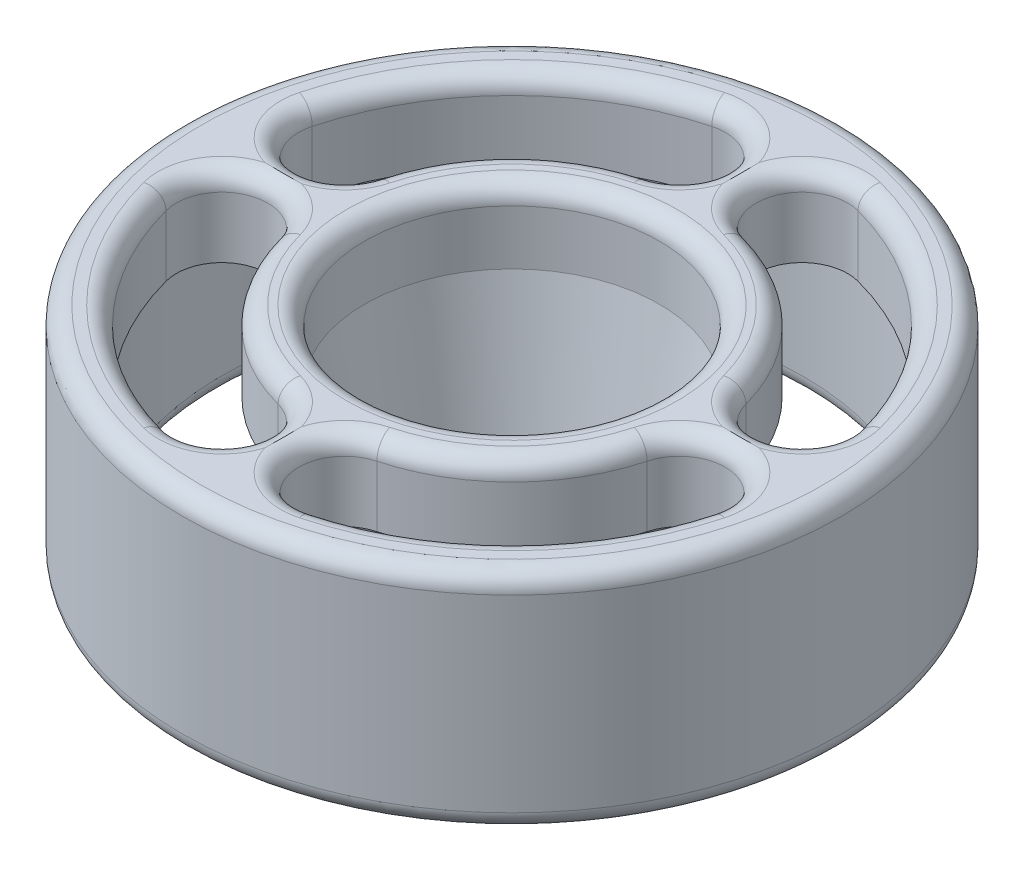
SolidWorks part; units mm, degrees
ref_plane "Front" through (0, 0, 0) normal (0, 0, 1) x (1, 0, 0)
ref_plane "Top" through (0, 0, 0) normal (0, 1, 0) x (1, 0, 0)
ref_plane "Right" through (0, 0, 0) normal (1, 0, 0) x (0, 0, -1)
sketch "Croquis1" plane through (0, 0, 0) normal (1, 0, 0) x (0, 0, -1)
  line L0 (-319.2356, 0) -> (15642.5458, 0) construction
  line L1 (0, -319.2356) -> (0, 15642.5458) construction
  line L3 (-6.6806, 2) -> (-8.0912, 10)
  line L4 (-8.0912, 10) -> (-8.0912, 14)
  line L5 (-8.0912, 14) -> (-18.0912, 14)
  line L6 (-18.0912, 14) -> (-18.0912, -2.75)
  line L7 (-319.2356, 2) -> (15642.5458, 2) construction
  line L8 (-6.6806, 2) -> (0, 2)
  line L9 (0, 2) -> (0, 0)
  line L10 (0, 0) -> (-3.25, 0)
  line L11 (-3.25, 0) -> (-3.25, -2.75)
  line L12 (-3.25, -2.75) -> (-18.0912, -2.75)
  dimension "D1" = 2
  dimension "D2" = 3.25
  dimension "D3" = 4
  dimension "D4" = 100
  dimension "D5" = 10
  dimension "D6" = 8
  dimension "D7" = 2.75
revolve "Revolución1" add sketch "Croquis1" angle 360 about L9
sketch "Croquis2" plane through (0, 2, 0) normal (0, 1, 0) x (1, 0, 0)
  circle A0 centre (0, 0) radius 1.125
  dimension "D1" = 2.25
extrude "Cortar-Extruir1" cut sketch "Croquis2" against normal through all
sketch "Croquis3" plane through (0, 0, 0) normal (1, 0, 0) x (0, 0, -1)
  line L0 (-1005.9461, -4.3493) -> (48994.0539, -4.3493) construction
  line L2 (-15.9567, -4.3493) -> (-15.9567, 9.6507)
  line L3 (-15.9567, 9.6507) -> (-9.9567, 9.6507)
  line L4 (-9.9567, 9.6507) -> (-7.9567, -4.3493)
  line L5 (0, -1000) -> (0, 49000) construction
  line L7 (-15.9567, -4.3493) -> (-7.9567, -4.3493)
  dimension "D1" = 14
  dimension "D2" = 8
  dimension "D3" = 6
revolve "Cortar-Revolución1" cut sketch "Croquis3" angle 360 about L5
sketch "Croquis5" plane through (0, 14, 0) normal (0, 1, 0) x (1, 0, 0)
  line L0 (-1000, 0) -> (49000, 0) construction
  line L1 (0, -1000) -> (0, 49000) construction
  line L2 (-707.1068, -707.1068) -> (34648.2323, 34648.2323) construction
  line L3 (-707.1068, 707.1068) -> (34648.2323, -34648.2323) construction
  line L4 (-702.5106, -711.703) -> (34652.8285, 34643.6361) construction
  line L5 (-711.703, -702.5106) -> (34643.6361, 34652.8285) construction
  circle A0 centre (0, 0) radius 13 construction
  circle A1 centre (0, 0) radius 15.5 construction
  circle A2 centre (0, 0) radius 10.5 construction
  arc A3 (3.3646, 12.557) -> (12.557, 3.3646) centre (0, 0) cw construction
  arc A4 (14.9835, 4.0148) -> (4.0148, 14.9835) centre (0, 0) ccw
  arc A5 (10.1306, 2.7145) -> (2.7145, 10.1306) centre (0, 0) ccw
  arc A6 (10.1306, 2.7145) -> (14.9835, 4.0148) centre (12.557, 3.3646) ccw
  arc A7 (4.0148, 14.9835) -> (2.7145, 10.1306) centre (3.3646, 12.557) ccw
  arc A8 (12.557, -3.3646) -> (3.3646, -12.557) centre (0, 0) cw construction
  arc A9 (4.0148, -14.9835) -> (14.9835, -4.0148) centre (0, 0) ccw
  arc A10 (2.7145, -10.1306) -> (10.1306, -2.7145) centre (0, 0) ccw
  arc A11 (2.7145, -10.1306) -> (4.0148, -14.9835) centre (3.3646, -12.557) ccw
  arc A12 (14.9835, -4.0148) -> (10.1306, -2.7145) centre (12.557, -3.3646) ccw
  arc A13 (-3.3646, -12.557) -> (-12.557, -3.3646) centre (0, 0) cw construction
  arc A14 (-14.9835, -4.0148) -> (-4.0148, -14.9835) centre (0, 0) ccw
  arc A15 (-10.1306, -2.7145) -> (-2.7145, -10.1306) centre (0, 0) ccw
  arc A16 (-10.1306, -2.7145) -> (-14.9835, -4.0148) centre (-12.557, -3.3646) ccw
  arc A17 (-4.0148, -14.9835) -> (-2.7145, -10.1306) centre (-3.3646, -12.557) ccw
  arc A18 (-12.557, 3.3646) -> (-3.3646, 12.557) centre (0, 0) cw construction
  arc A19 (-4.0148, 14.9835) -> (-14.9835, 4.0148) centre (0, 0) ccw
  arc A20 (-2.7145, 10.1306) -> (-10.1306, 2.7145) centre (0, 0) ccw
  arc A21 (-2.7145, 10.1306) -> (-4.0148, 14.9835) centre (-3.3646, 12.557) ccw
  arc A22 (-14.9835, 4.0148) -> (-10.1306, 2.7145) centre (-12.557, 3.3646) ccw
  point P22 (9.1924, 9.1924)
  point P32 (9.1924, -9.1924)
  point P39 (-9.1924, -9.1924)
  point P46 (-9.1924, 9.1924)
  point P51 (0, 0)
  dimension "D1" = 26
  dimension "D2" = 2.5
  dimension "D3" = 2.5
  dimension "D4" = 6.5
  dimension "D5" = 6.5
  dimension "D6" = 4
extrude "Cortar-Extruir3" cut sketch "Croquis5" against normal blind 12
fillet "Redondeo1" radius 1 20 edges at (0, 14, 8.0912) (-0.9382, 14, -13.2072) (-13.2072, 14, -0.9382) (-7.4161, 14, -7.4161) (-10.9687, 14, -10.9687) (0, 14, 18.0912) (0.9382, 14, -13.2072) (10.9687, 14, -10.9687) (7.4161, 14, -7.4161) (13.2072, 14, -0.9382) (13.2072, 14, 0.9382) (7.4161, 14, 7.4161) (10.9687, 14, 10.9687) (0.9382, 14, 13.2072) (-0.9382, 14, 13.2072) (-10.9687, 14, 10.9687) (-13.2072, 14, 0.9382) (-7.4161, 14, 7.4161) (0, -2.75, 3.25) (0, -2.75, -8.1852)
sketch "Croquis6" plane through (0, 0, 0) normal (1, 0, 0) x (0, 0, -1)
  line L0 (-1000, 0) -> (49000, 0) construction
  line L1 (0, -1000) -> (0, 49000) construction
  line L2 (-18.0912, 13) -> (-18.0912, -2.75) construction
  line L3 (-1009.5589, -4.3493) -> (48990.4411, -4.3493) construction
  line L5 (-18.0912, -4.3493) -> (-15.9567, -4.3493)
  line L8 (-15.9567, -4.3493) -> (-15.9567, 1.6507)
  line L9 (-15.9567, 1.6507) -> (-18.0912, 1.6507)
  line L10 (-18.0912, -4.3493) -> (-18.0912, 1.6507)
  dimension "D1" = 6
revolve "Cortar-Revolución2" cut sketch "Croquis6" angle 360 about L1
fillet "Redondeo2" radius 1 2 edges at (0, 1.6507, -15.9567) (0, 1.6507, -18.0912)
